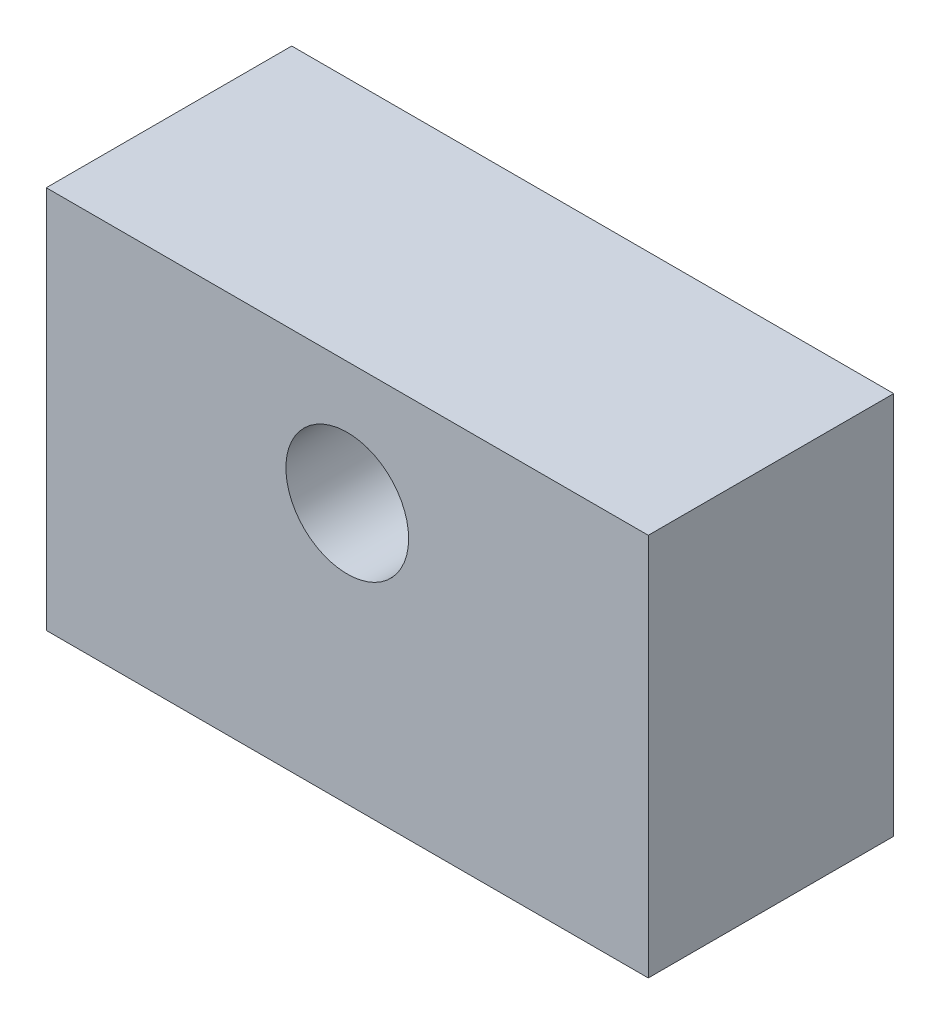
SolidWorks part; units mm, degrees
material "1060 Alloy"
ref_plane "Front" through (0, 0, 0) normal (0, 0, 1) x (1, 0, 0)
ref_plane "Top" through (0, 0, 0) normal (0, 1, 0) x (1, 0, 0)
ref_plane "Right" through (0, 0, 0) normal (1, 0, 0) x (0, 0, -1)
sketch "Sketch3" plane through (0, 0, 0) normal (0, 0, 1) x (1, 0, 0)
  line L0 (-0.127, -6.35) -> (30.1755, -6.35)
  line L1 (0, 0) -> (31.1484, 0)
  line L2 (0, 0) -> (0, -19.8376)
  line L3 (0, -19.8376) -> (31.1484, -19.8376)
  line L4 (31.1484, 0) -> (31.1484, -19.8376)
  line L5 (15.5742, -19.8376) -> (15.5742, 0) construction
  line L6 (15.5742, -6.35) -> (8.0621, -19.3614) construction
  line L15 (12.5496, -11.5887) -> (15.5742, -13.335) construction
  line L16 (15.5742, -6.35) -> (22.9274, -19.0862) construction
  circle A0 centre (15.5742, -6.35) radius 6.0492 construction
  point P14 (0, -6.35)
  point P17 (9.525, -6.35)
  point P19 (31.1484, -6.35)
  point P20 (7.7871, -19.8376)
  point P24 (23.3613, -19.8376)
  dimension "D2" = 6.35
  dimension "D6" = 3.4925
  dimension "D3" = 60
  dimension "D1" = 9.525
  dimension "D4" = 9.525
  dimension "D5" = 60
extrude "Boss-Extrude1" add sketch "Sketch3" along normal mid plane 12.7
sketch "Sketch4" plane through (0, 0, 0) normal (-1, 0, 0) x (0, 0, 1)
  circle A0 centre (0, -6.35) radius 3.175
  dimension "D1" = 6.35
extrude "Cut-Extrude1" cut sketch "Sketch4" against normal blind 9.525
ref_plane "Plane1" through (7.7871, -19.8376, 0) normal (-0.5, -0.866, 0) x (-0.866, 0.5, 0)
ref_plane "Mirror Plane" through (15.5742, 0, 0) normal (-1, 0, 0) x (0, 0, 1)
sketch "Sketch5" plane through (7.7871, -19.8376, 0) normal (-0.5, -0.866, 0) x (-0.866, 0.5, 0)
  circle A0 centre (0, 0) radius 3.175
  dimension "D1" = 6.35
extrude "Cut-Extrude5" cut sketch "Sketch5" against normal blind 9.525 and the other way up to next
sketch "Sketch6" plane through (0, 0, 6.35) normal (0, 0, -1) x (-1, 0, 0)
  circle A0 centre (-15.5742, -6.35) radius 3.175
  dimension "D1" = 6.35
extrude "Cut-Extrude6" cut sketch "Sketch6" along normal blind 9.525
mirror "Mirror1" about plane through (15.5742, 0, 0) normal (-1, 0, 0) of "Cut-Extrude5"
equation "\"truss_member_od\"= .25in"
equation "\"truss_member_id\"= 0in"
equation "\"truss_member_L1\"= 2.125in"
equation "\"connector_hole_depth\"= .375in"
equation "\"D1@Boss-Extrude1\"=\"truss_member_od\"*2"
equation "\"D6@Sketch3\"=\"truss_member_od\"/2*1.1"
equation "\"D1@Sketch4\"=\"truss_member_od\""
equation "\"D1@Cut-Extrude1\"=\"connector_hole_depth\""
equation "\"D1@Sketch3\"=\"connector_hole_depth\""
equation "\"D4@Sketch3\"=\"connector_hole_depth\""
equation "\"D1@Sketch5\"=\"truss_member_od\""
equation "\"D1@Cut-Extrude5\"=\"connector_hole_depth\""
equation "\"D1@Cut-Extrude6\"=\"connector_hole_depth\""
equation "\"D1@Sketch6\"=\"truss_member_od\""
